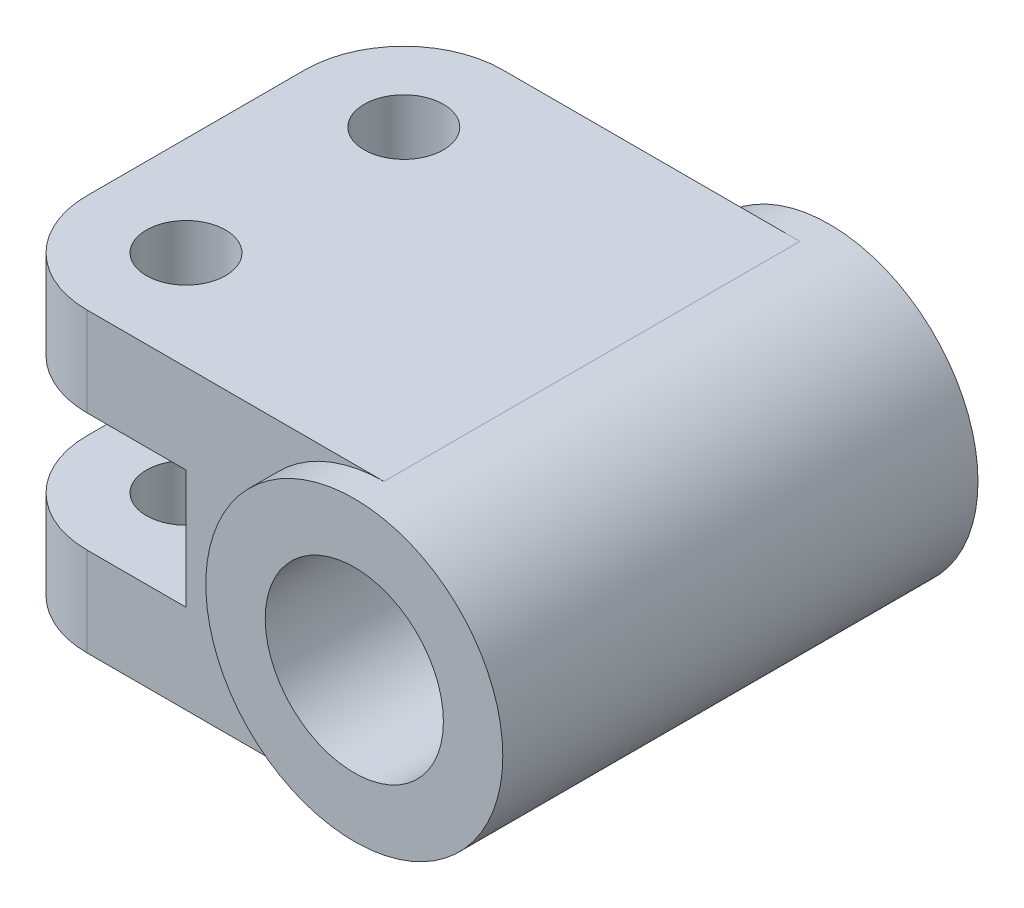
SolidWorks part; units mm, degrees
ref_plane "前视基准面" through (0, 0, 0) normal (0, 0, 1) x (1, 0, 0)
ref_plane "上视基准面" through (0, 0, 0) normal (0, 1, 0) x (1, 0, 0)
ref_plane "右视基准面" through (0, 0, 0) normal (1, 0, 0) x (0, 0, -1)
other "Configuration Table"
sketch "草图1" plane through (0, 0, 0) normal (0, 0, 1) x (1, 0, 0)
  line L0 (0, 0) -> (40, 0)
  line L1 (0, 0) -> (0, 9)
  line L2 (0, 9) -> (20, 9)
  line L3 (20, 9) -> (20, 21)
  line L4 (20, 15) -> (57.5735, 15) construction
  line L5 (0, 21) -> (20, 21)
  line L6 (0, 30) -> (0, 21)
  line L7 (0, 30) -> (40, 30)
  arc A0 (40, 0) -> (40, 30) centre (40, 15) ccw
  circle A1 centre (40, 15) radius 9
  arc A2 (40, 30) -> (40, 0) centre (40, 15) ccw
  dimension "D1" = 20
  dimension "D2" = 9
  dimension "D3" = 6
  dimension "D4" = 40
extrude "凸台-拉伸1" add sketch "草图1" along normal blind 42 contours L4 A2 A0 A1 | L3 L4 A2 L7 L6 L5 | A2 L4 A1 A0 | L4 L3 L2 L1 L0 A2 region at (16.0127, 5.0589, 0) region at (29.6306, 4.6306, 0) region at (52, 15.3354, 0) region at (16.0127, 24.9411, 0)
sketch "草图2" plane through (0, 0, 42) normal (0, 0, 1) x (1, 0, 0)
  circle A0 centre (40, 15) radius 9
  circle A1 centre (40, 15) radius 15
extrude "凸台-拉伸3" add sketch "草图2" along normal blind 3 and the other way blind 45
sketch "草图3" plane through (0, 30, 0) normal (0, 1, 0) x (1, 0, 0)
  line L0 (0, 0) -> (40, 0) construction
  line L1 (0, -42) -> (0, 0) construction
  circle A0 centre (10, -10) radius 10
  circle A1 centre (10, -10) radius 4
extrude "切除-拉伸1" cut sketch "草图3" against normal through all both and the other way through all contours A1
sketch "草图4" plane through (0, 30, 0) normal (0, 1, 0) x (1, 0, 0)
  circle A1 centre (10, -32) radius 4
extrude "切除-拉伸2" cut sketch "草图4" against normal through all both and the other way through all
fillet "圆角5" radius 10 4 edges at (0, 25.5, 0) (0, 4.5, 0) (0, 4.5, 42) (0, 25.5, 42)
